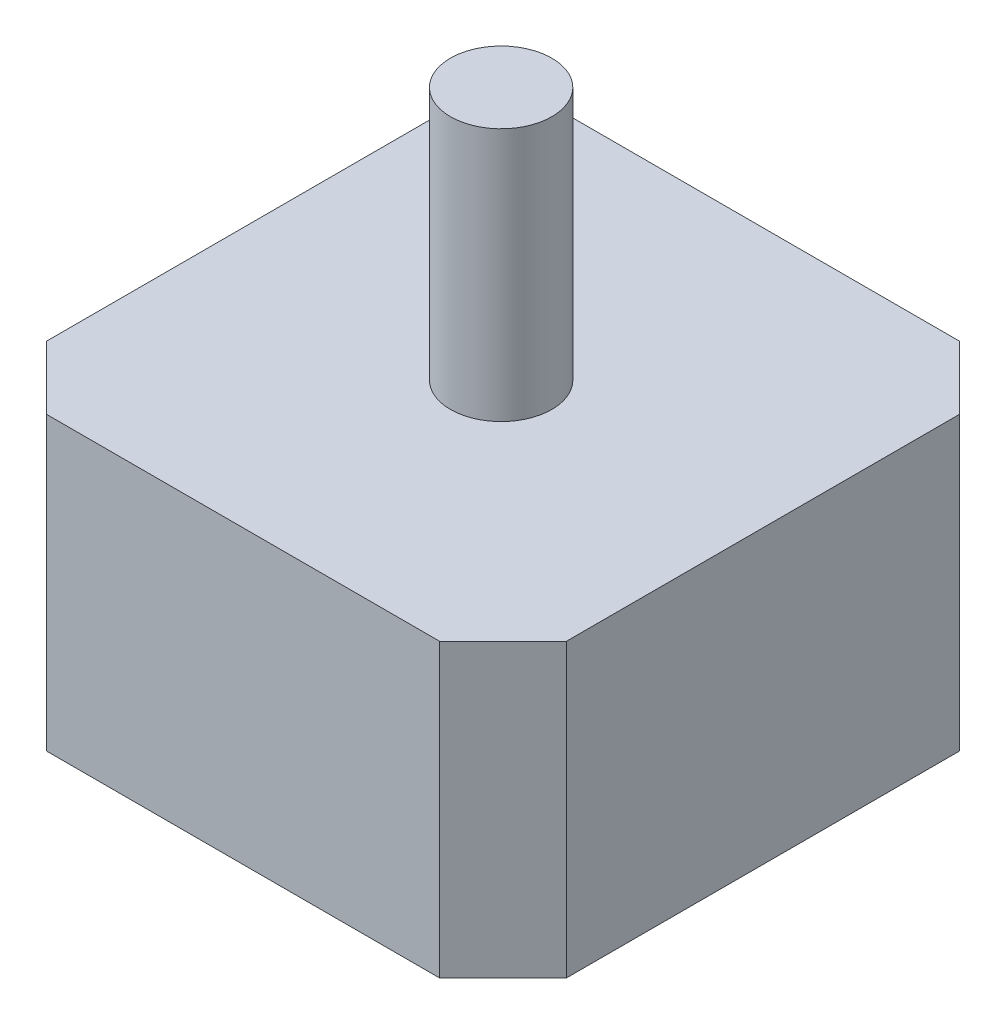
SolidWorks part; units mm, degrees
ref_plane "Front Plane" through (0, 0, 0) normal (0, 0, 1) x (1, 0, 0)
ref_plane "Top Plane" through (0, 0, 0) normal (0, 1, 0) x (1, 0, 0)
ref_plane "Right Plane" through (0, 0, 0) normal (1, 0, 0) x (0, 0, -1)
sketch "Sketch2" plane through (0, 0, 0) normal (0, 1, 0) x (1, 0, 0)
  line L0 (-20.5, 20.5) -> (-7.4847, 20.5) construction
  line L1 (-20.5, 20.5) -> (20.5, 20.5)
  line L2 (-20.5, 20.5) -> (-20.5, -20.5)
  line L3 (-20.5, -20.5) -> (20.5, -20.5)
  line L4 (20.5, 20.5) -> (20.5, -20.5)
  line L5 (0, -20.5) -> (0, 20.5) construction
  line L6 (-20.5, 0) -> (20.5, 0) construction
  line L7 (20.5, 20.5) -> (7.5093, 20.5) construction
  line L8 (7.5093, 20.5) -> (7.5093, 24.5028) construction
  line L9 (7.5093, 24.5028) -> (-7.4847, 24.5028) construction
  line L11 (-7.4847, 20.5) -> (7.5093, 20.5)
  line L12 (-7.4847, 20.5) -> (-7.4847, 24.5028)
  line L13 (-7.4847, 24.5028) -> (7.5093, 24.5028)
  line L14 (7.5093, 20.5) -> (7.5093, 24.5028)
  point P0 (0, 0)
  dimension "D1" = 41
  dimension "D2" = 41
extrude "Boss-Extrude7" add sketch "Sketch2" along normal blind 23 contours L4 L1 L2 L3 | L1 L14 L13 L12 region at (0, 0, 0) region at (0.0123, 0, -22.5014)
sketch "Sketch3" plane through (0, 23, 0) normal (0, 1, 0) x (1, 0, 0)
  circle A0 centre (0, 0) radius 4
sketch "Sketch5" plane through (37.5, 23, -1.3023) normal (0, 1, 0) x (1, 0, 0)
  circle A0 centre (-37.4046, -1.5445) radius 4
extrude "Boss-Extrude8" add sketch "Sketch5" along normal blind 20 separate body
sketch "Sketch6" plane through (0, 0, 0) normal (0, 1, 0) x (1, 0, 0)
  line L0 (-20.5, 20.5) -> (-15.5, 20.5)
  line L1 (-20.5, 20.5) -> (-7.4847, 20.5) construction
  line L2 (-20.5, 20.5) -> (-20.5, 15.5)
  line L3 (-20.5, 20.5) -> (-20.5, -20.5) construction
  line L4 (-20.5, 15.5) -> (-15.5, 20.5)
extrude "Cut-Extrude1" cut sketch "Sketch6" along normal blind 23 contours L0 L4 L2
sketch "Sketch7" plane through (0, 0, 0) normal (0, 1, 0) x (1, 0, 0)
  line L0 (-20.5, -20.5) -> (-20.5, -15.5)
  line L1 (-20.5, 15.5) -> (-20.5, -20.5) construction
  line L2 (-20.5, -20.5) -> (-15.5, -20.5)
  line L3 (-20.5, -20.5) -> (20.5, -20.5) construction
  line L4 (-20.5, -15.5) -> (-15.5, -20.5)
  line L5 (20.5, -20.5) -> (15.5, -20.5)
  line L6 (20.5, -20.5) -> (20.5, -15.5)
  line L7 (20.5, 20.5) -> (20.5, -20.5) construction
  line L8 (20.5, -15.5) -> (15.5, -20.5)
  line L9 (20.5, 20.5) -> (20.5, 15.5)
  line L10 (20.5, 20.5) -> (15.5, 20.5)
  line L11 (7.5093, 20.5) -> (20.5, 20.5) construction
  line L12 (15.5, 20.5) -> (20.5, 15.5)
extrude "Cut-Extrude3" cut sketch "Sketch7" along normal blind 23 contours L4 L2 L0 | L8 L5 L6 | L12 L9 L10
sketch "Sketch8" plane through (0, 23, 0) normal (0, 1, 0) x (1, 0, 0)
  line L0 (-7.4847, 20.5) -> (7.5093, 20.5)
  line L1 (7.5093, 20.5) -> (7.5093, 24.5028)
  line L2 (7.5093, 24.5028) -> (-7.4847, 24.5028)
  line L3 (-7.4847, 24.5028) -> (-7.4847, 20.5)
extrude "Cut-Extrude4" cut sketch "Sketch8" against normal blind 14 contours L3 L0 L1 L2
